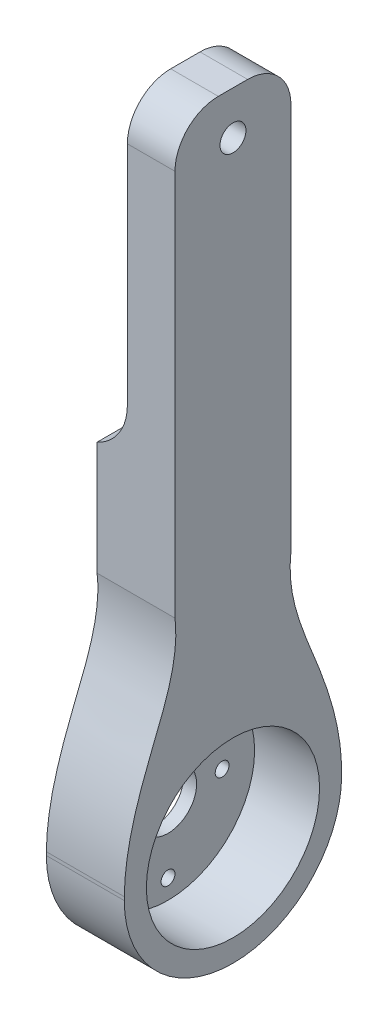
SolidWorks part; units mm, degrees
ref_plane "前视基准面" through (0, 0, 0) normal (0, 0, 1) x (1, 0, 0)
ref_plane "上视基准面" through (0, 0, 0) normal (0, 1, 0) x (1, 0, 0)
ref_plane "右视基准面" through (0, 0, 0) normal (1, 0, 0) x (0, 0, -1)
sketch "Sketch1" plane through (0, 0, 0) normal (1, 0, 0) x (0, 0, -1)
  circle A0 centre (2.9834, 10.8268) radius 7.75 construction
  circle A1 centre (2.9834, 10.8268) radius 6.25 construction
  circle A2 centre (2.9834, 18.5768) radius 0.8
  circle A3 centre (2.9834, 3.0768) radius 0.8
  circle A4 centre (-3.2666, 10.8268) radius 0.8
  circle A5 centre (9.2334, 10.8268) radius 0.8
  circle A6 centre (2.9834, 10.8268) radius 10
  circle A7 centre (2.9834, 10.8268) radius 3.3018
  dimension "D1" = 15.5
  dimension "D2" = 12.5
  dimension "D3" = 20
extrude "Boss-Extrude1" add sketch "Sketch1" along normal blind 1.5
sketch "Sketch2" plane through (0, 0, 0) normal (-1, 0, 0) x (0, 0, 1)
  line L0 (-2.9834, 10.8268) -> (-2.9834, 25.4318) construction
  line L2 (-12.9834, 85.8268) -> (7.0166, 85.8268) construction
  line L3 (-12.9834, 85.8268) -> (-12.9834, 10.8268) construction
  line L4 (-12.9834, 10.8268) -> (7.0166, 10.8268) construction
  line L5 (7.0166, 85.8268) -> (7.0166, 10.8268) construction
  line L6 (-12.9834, 85.8268) -> (7.0166, 10.8268) construction
  line L7 (-12.9834, 10.8268) -> (7.0166, 85.8268) construction
  line L8 (-15.5319, 85.8268) -> (9.5652, 85.8268)
  line L9 (-15.5319, 85.8268) -> (-15.5319, 10.8268)
  line L10 (-15.5319, 10.8268) -> (9.5652, 10.8268) construction
  line L11 (9.5652, 85.8268) -> (9.5652, 10.8268)
  line L12 (-15.5319, 85.8268) -> (9.5652, 10.8268) construction
  line L13 (-15.5319, 10.8268) -> (9.5652, 85.8268) construction
  circle A0 centre (-2.9834, 10.8268) radius 10 construction
  arc A1 (-12.9834, 10.8268) -> (7.0166, 10.8268) centre (-2.9834, 10.8268) cw construction
  circle A2 centre (-2.9834, 10.8268) radius 12.5485 construction
  circle A3 centre (-2.9834, 10.8268) radius 10
  arc A4 (-15.5319, 10.8268) -> (9.5652, 10.8268) centre (-2.9834, 10.8268) ccw
  circle A5 centre (-2.9834, 10.8268) radius 0.6321 construction
  point P1 (-2.9834, 48.3268)
  point P12 (-2.9834, 48.3268)
  dimension "D1" = 0
  dimension "D2" = 75
extrude "Boss-Extrude2" add sketch "Sketch2" against normal blind 9
sketch "Sketch3" plane through (9, 0, 0) normal (1, 0, 0) x (0, 0, -1)
  line L0 (2.9834, 95.8916) -> (2.9834, 22.8694) construction
  line L1 (-9.5652, 85.8268) -> (15.5319, 85.8268) construction
  line L3 (-3.7095, 36.1504) -> (-3.7095, 97.5726)
  line L4 (-3.7095, 97.5726) -> (-16.389, 97.5726)
  line L5 (-16.389, 97.5726) -> (-16.389, 8.1411)
  line L6 (-16.389, 8.1411) -> (-9.5652, 10.8268)
  line L7 (22.3558, 8.1411) -> (15.5319, 10.8268)
  line L8 (22.3558, 97.5726) -> (22.3558, 8.1411)
  line L9 (9.6763, 97.5726) -> (22.3558, 97.5726)
  line L10 (9.6763, 36.1504) -> (9.6763, 97.5726)
  circle A0 centre (2.9834, 80.8268) radius 1.5
  spline S0 degree 3 poles (-9.5652, 10.8268) (-9.6028, 15.1167) (-7.0859, 23.5011) (-3.1551, 31.4702) (-3.7095, 36.1504) knots 0 0 0 0 0.483956 1 1 1 1
  spline S1 degree 3 poles (15.5319, 10.8268) (15.5695, 15.1167) (13.0527, 23.5011) (9.1219, 31.4702) (9.6763, 36.1504) knots 0 0 0 0 0.483956 1 1 1 1
  point P9 (2.9834, 75.2574)
  dimension "D1" = 5
extrude "Cut-Extrude1" cut sketch "Sketch3" against normal through all both and the other way through all
fillet "Fillet1" radius 5 2 edges at (4.5, 85.8268, -9.6763) (4.5, 85.8268, 3.7095)
sketch "Sketch4" plane through (0, 0, -9.6763) normal (0, 0, -1) x (-1, 0, 0)
  line L1 (-3.5, 95.8916) -> (7.5428, 95.8916)
  line L2 (-3.5, 95.8916) -> (-3.5, 49.2405)
  line L3 (-3.5, 49.2405) -> (7.5428, 49.2405)
  line L4 (7.5428, 95.8916) -> (7.5428, 49.2405)
  line L6 (-9, 36.1504) -> (-9, 80.8268) construction
  dimension "D1" = 5.5
extrude "Cut-Extrude2" cut sketch "Sketch4" against normal through all both and the other way through all
fillet "Fillet3" radius 6 1 edges at (3.5, 49.2405, -2.9834)
